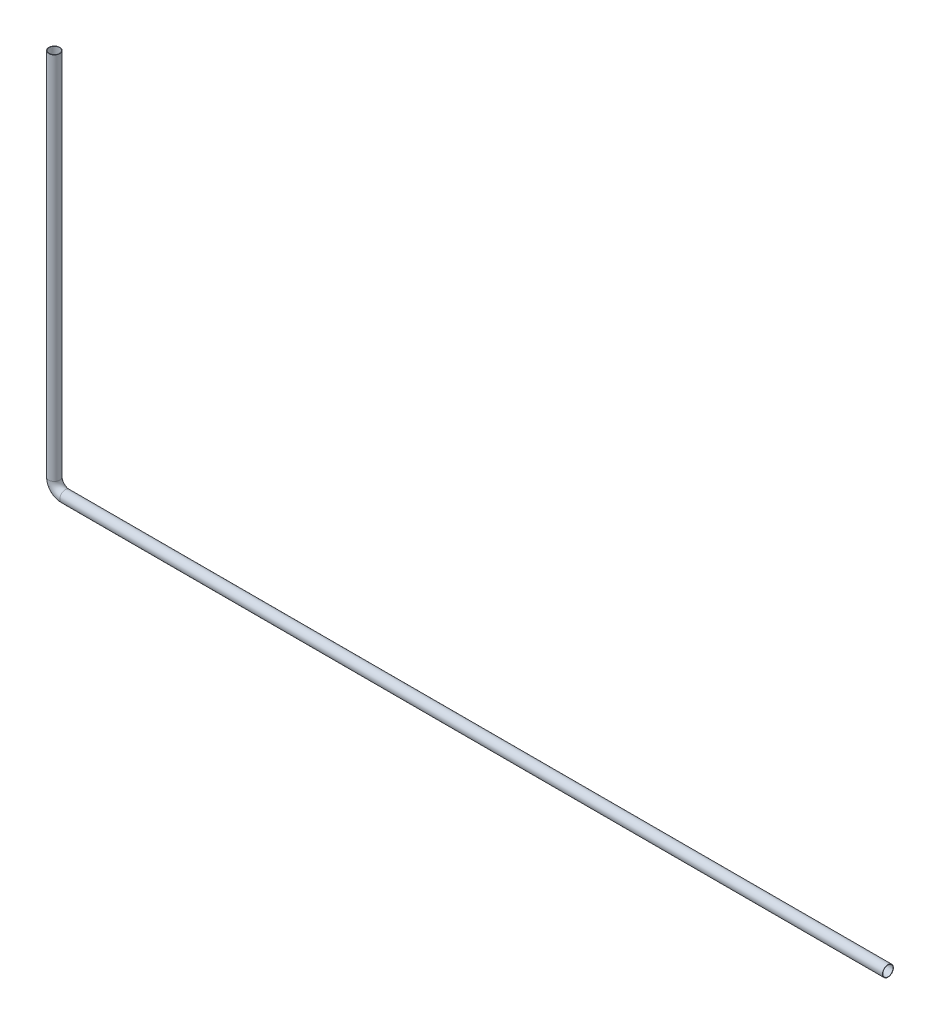
SolidWorks part; units mm, degrees
ref_plane "Plano frontal" through (0, 0, 0) normal (0, 0, 1) x (1, 0, 0)
ref_plane "Plano superior" through (0, 0, 0) normal (0, 1, 0) x (1, 0, 0)
ref_plane "Plano direito" through (0, 0, 0) normal (1, 0, 0) x (0, 0, -1)
sketch3d "3DSketch1"
  line L0 (-34220.2161, -16256.7026, 40211.5777) -> (-34220.2161, -17268.2109, 40211.5777)
  line L2 (-34220.2161, -16256.7026, 32891.1068) -> (-34220.2161, -16256.7026, 42891.1068) construction
  line L3 (-34190.2161, -17298.2109, 40211.5777) -> (-31937.4493, -17298.2109, 40211.5777)
  line L4 (-31937.4493, -17298.2109, 41543.1604) -> (-31937.4493, -17298.2109, 39237.3639) construction
  arc A0 (-34190.2161, -17298.2109, 40211.5777) -> (-34220.2161, -17268.2109, 40211.5777) centre (-34190.2161, -17268.2109, 40211.5777) ccw
  point P5 (0, 0, 0)
  point P10 (-34220.2161, -17298.2109, 40211.5777)
  point P11 (-34190.2161, -17268.2109, 40181.5777)
  point P12 (-34220.2161, -16256.7026, 40211.5777)
  dimension "D1" = 30
sweep "Sweep-Thin1" add path "3DSketch1" circular profile diameter 30 parameters "D1"=1, "D3"=30
